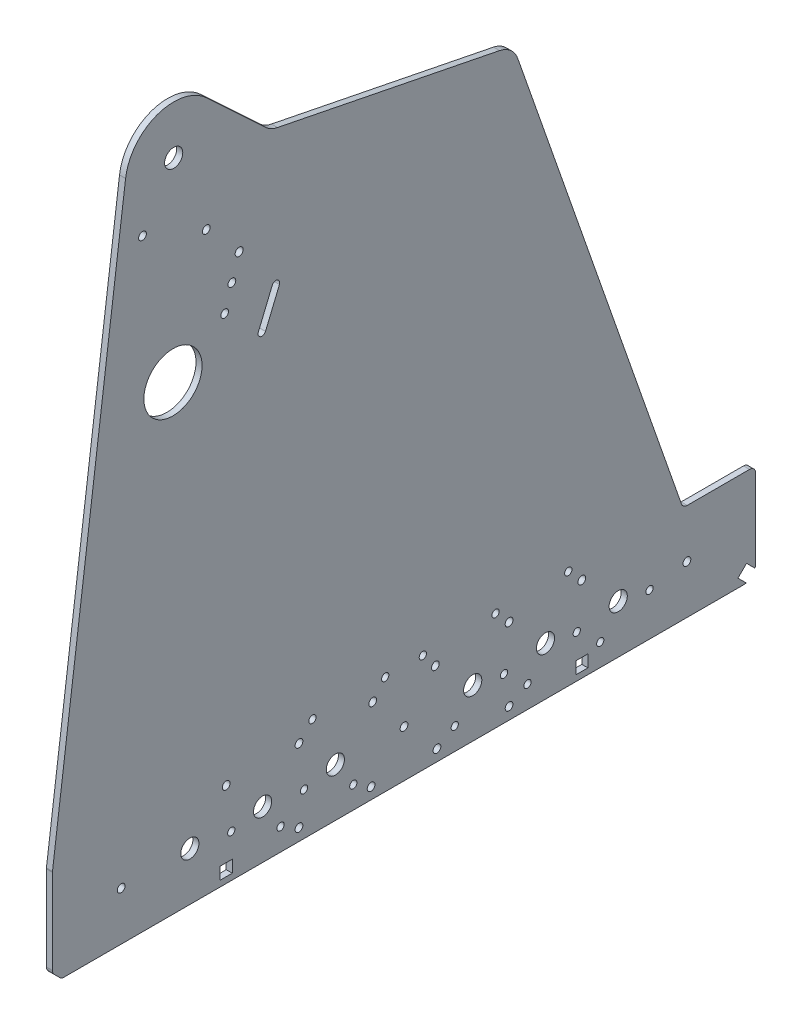
SolidWorks part; units mm, degrees
ref_plane "Front Plane" through (0, 0, 0) normal (0, 0, 1) x (1, 0, 0)
ref_plane "Top Plane" through (0, 0, 0) normal (0, 1, 0) x (1, 0, 0)
ref_plane "Right Plane" through (0, 0, 0) normal (1, 0, 0) x (0, 0, -1)
sketch "Sketch1" plane through (0, 0, 0) normal (1, 0, 0) x (0, 0, -1)
  line L0 (-184.15, -24.6062) -> (184.15, -24.6062)
  line L1 (184.15, -24.6062) -> (184.15, 26.1938)
  line L2 (184.15, 26.1938) -> (146.05, 26.1937)
  line L3 (146.05, 26.1937) -> (57.15, 280.1938)
  line L5 (-145.839, 321.5609) -> (-184.15, 26.1938)
  line L6 (-184.15, 26.1938) -> (-184.15, -24.6062)
  line L7 (-184.15, 350.0437) -> (184.15, 350.0437) construction
  line L8 (57.15, 280.1938) -> (-69.85, 305.5938)
  line L9 (-69.85, 305.5938) -> (-103.3099, 336.854)
  arc A0 (-103.3099, 336.854) -> (-145.839, 321.5609) centre (-120.65, 318.2937) ccw
  point P8 (0, -24.6062)
  dimension "D1" = 368.3
  dimension "D7" = 25.4
  dimension "D2" = 50.8
  dimension "D3" = 38.1
  dimension "D4" = 24.6062
  dimension "D5" = 374.65
  dimension "D6" = 304.8
  dimension "D8" = 342.9
  dimension "D9" = 127
  dimension "D10" = 304.8
  dimension "D11" = 25.4
  dimension "D12" = 127
extrude "Boss-Extrude1" add sketch "Sketch1" along normal blind 3.175
chamfer "Chamfer1" distance 4.7625 angle 45 2 edges at (1.5875, -24.6062, 184.15) (1.5875, -24.6062, -184.15)
fillet "Fillet1" radius 12.7 2 edges at (1.5875, 305.5938, 69.85) (1.5875, 280.1938, -57.15)
fillet "Fillet2" radius 3.175 3 edges at (1.5875, 26.1938, 184.15) (1.5875, 26.1938, -184.15) (1.5875, 26.1937, -146.05)
fillet "Fillet3" radius 3.175 4 edges at (1.5875, -19.8438, -184.15) (1.5875, -24.6062, -179.3875) (1.5875, -19.8437, 184.15) (1.5875, -24.6062, 179.3875)
sketch "Sketch16" plane through (3.175, 0, 0) normal (1, 0, 0) x (0, 0, -1)
  circle A0 centre (112.1746, 0.7937) radius 4.7625
  circle A1 centre (74.0746, 0.7937) radius 4.7625
  circle A2 centre (35.9746, 0.7937) radius 4.7625
  circle A3 centre (-35.9746, 0.7938) radius 4.7625
  circle A4 centre (-74.0746, 0.7938) radius 4.7625
  circle A5 centre (-112.1746, 0.7937) radius 4.7625
  dimension "D1" = 9.525
  dimension "D2" = 9.525
extrude "Cut-Extrude1" cut sketch "Sketch16" against normal up to next
sketch "Sketch25" plane through (3.175, 0, 0) normal (1, 0, 0) x (0, 0, -1)
  circle A0 centre (102.7672, -13.0003) radius 1.905 construction
  circle A1 centre (86.0486, 27.3622) radius 1.905 construction
  circle A2 centre (128.5804, -2.3081) radius 1.905 construction
  circle A3 centre (102.7672, -13.0003) radius 1.905
  circle A4 centre (86.0486, 27.3622) radius 1.905
  circle A5 centre (128.5804, -2.3081) radius 1.905
  circle A6 centre (64.6672, -13.0003) radius 1.905 construction
  circle A8 centre (-9.8486, 27.3622) radius 1.905 construction
  circle A10 centre (-47.9486, 27.3622) radius 1.905 construction
  circle A11 centre (-90.4804, -2.3081) radius 1.905 construction
  circle A12 centre (-64.6672, -13.0003) radius 1.905 construction
  circle A14 centre (-52.3804, -2.3081) radius 1.905 construction
  circle A15 centre (-26.5672, -13.0003) radius 1.905 construction
  circle A16 centre (9.8486, 27.3622) radius 1.905 construction
  circle A17 centre (26.5672, -13.0003) radius 1.905 construction
  circle A18 centre (47.9486, 27.3622) radius 1.905 construction
  circle A19 centre (52.3804, -2.3081) radius 1.905 construction
  circle A20 centre (90.4804, -2.3081) radius 1.905 construction
  circle A21 centre (-9.8486, 27.3622) radius 1.905
  circle A23 centre (-47.9486, 27.3622) radius 1.905
  circle A24 centre (-90.4804, -2.3081) radius 1.905
  circle A25 centre (-64.6672, -13.0003) radius 1.905
  circle A27 centre (-52.3804, -2.3081) radius 1.905
  circle A28 centre (-26.5672, -13.0003) radius 1.905
  circle A29 centre (9.8486, 27.3622) radius 1.905
  circle A30 centre (26.5672, -13.0003) radius 1.905
  circle A31 centre (47.9486, 27.3622) radius 1.905
  circle A32 centre (64.6672, -13.0003) radius 1.905
  circle A33 centre (52.3804, -2.3081) radius 1.905
  circle A34 centre (90.4804, -2.3081) radius 1.905
extrude "Cut-Extrude4" cut sketch "Sketch25" against normal up to next
sketch "Sketch23" plane through (3.175, 0, 0) normal (1, 0, 0) x (0, 0, -1)
  point P0 (-55.0246, -18.3223)
  point P3 (-55.0246, 19.9098)
  point P6 (-93.1246, 19.9098)
  point P9 (-17.2515, -18.6426)
  point P12 (-16.4124, 19.3854)
  point P15 (16.4124, 19.3854)
  point P18 (17.2515, -18.6426)
  point P21 (55.0246, -18.3223)
  point P27 (93.1246, 19.9098)
  point P30 (55.0246, 19.9098)
hole_wizard "#8 (0.16) Diameter Hole1" positions "Sketch23" profile "Sketch24" hole size "#8" standard "ANSI Inch" end condition up to next
sketch "Sketch24" plane through (3.175, -18.3223, 55.0246) normal (0, 1, 0) x (0, 0, -1)
  line L0 (0, 0) -> (0, 3.175)
  line L1 (0, 3.175) -> (2.032, 3.175)
  line L2 (2.032, 3.175) -> (2.032, 0)
  line L5 (2.032, 0) -> (0, 0)
  line L11 (0, -6.35) -> (0, 107.95) construction
  dimension "Thru Hole Dia." = 4.064
  dimension "Thru Hole Depth" = 3.175
sketch "Sketch22" plane through (3.175, 0, 0) normal (1, 0, 0) x (0, 0, -1)
  line L0 (-96.2996, -15.1473) -> (-89.9496, -15.1473) construction
  line L1 (-96.2996, -15.1473) -> (-89.9496, -15.1473)
  line L2 (-96.2996, -15.1473) -> (-96.2996, -21.4973)
  line L3 (-96.2996, -21.4973) -> (-89.9496, -21.4973)
  line L4 (-89.9496, -15.1473) -> (-89.9496, -21.4973)
  line L5 (-96.2996, -15.1473) -> (-89.9496, -21.4973) construction
  line L6 (-96.2996, -21.4973) -> (-89.9496, -15.1473) construction
  line L7 (-89.9496, -15.1473) -> (-89.9496, -19.8734) construction
  line L77 (179.3875, -24.6062) -> (183.8776, -20.1161)
  line L78 (179.3875, -24.6062) -> (174.8974, -20.1161)
  line L79 (183.8776, -20.1161) -> (179.3875, -15.626)
  line L80 (174.8974, -20.1161) -> (179.3875, -15.626)
  line L81 (180.3174, -23.6763) -> (183.2201, -20.7737) construction
  line L82 (-178.0724, -24.6062) -> (178.0724, -24.6062) construction
  line L84 (89.9496, -21.4973) -> (96.2996, -21.4973)
  line L85 (89.9496, -21.4973) -> (89.9496, -15.1473)
  line L86 (89.9496, -15.1473) -> (96.2996, -15.1473)
  line L87 (96.2996, -21.4973) -> (96.2996, -15.1473)
  line L88 (89.9496, -21.4973) -> (96.2996, -15.1473) construction
  line L89 (89.9496, -15.1473) -> (96.2996, -21.4973) construction
  point P0 (-93.1246, -18.3223)
  point P19 (93.1246, -18.3223)
  dimension "D1" = 6.35
  dimension "D2" = 6.35
extrude "Cut-Extrude3" cut sketch "Sketch22" against normal up to next
sketch "Sketch21" plane through (3.175, 0, 0) normal (1, 0, 0) x (0, 0, -1)
  circle A0 centre (-148.1579, 0.7937) radius 2.032
  circle A2 centre (0, 0) radius 2.032
  circle A3 centre (148.1579, 0.7938) radius 2.032
  dimension "D1" = 4.064
extrude "Cut-Extrude2" cut sketch "Sketch21" against normal up to next
sketch "Sketch26" plane through (3.175, 0, 0) normal (1, 0, 0) x (0, 0, -1)
  line L0 (-145.839, 321.5609) -> (-184.1236, 26.3971) construction
  line L1 (-178.0724, -24.6062) -> (178.0724, -24.6062) construction
  circle A0 centre (-121.0218, 216.6937) radius 15.24
  dimension "D1" = 30.48
  dimension "D2" = 38.1
  dimension "D3" = 241.3
extrude "Cut-Extrude5" cut sketch "Sketch26" against normal through all
sketch "Sketch27" plane through (3.175, 0, 0) normal (1, 0, 0) x (0, 0, -1)
  circle A0 centre (-120.65, 318.2937) radius 4.7625
  dimension "D1" = 9.525
extrude "Cut-Extrude6" cut sketch "Sketch27" against normal through all
sketch "Sketch28" plane through (3.175, 0, 0) normal (1, 0, 0) x (0, 0, -1)
  line L0 (-120.65, 318.2937) -> (-103.5612, 277.2599) construction
  line L1 (-103.5612, 277.2599) -> (-86.3654, 258.566) construction
  line L2 (-86.3654, 258.566) -> (-90.1612, 246.4465) construction
  line L3 (-90.1612, 246.4465) -> (-93.9569, 234.327) construction
  line L4 (-145.839, 321.5609) -> (-184.1236, 26.3971) construction
  circle A0 centre (-93.9569, 234.327) radius 2.032
  circle A1 centre (-90.1612, 246.4465) radius 2.032
  circle A2 centre (-86.3654, 258.566) radius 2.0955
  circle A3 centre (-103.5612, 277.2599) radius 2.032
  dimension "D4" = 4.064
  dimension "D5" = 4.191
  dimension "D6" = 4.064
  dimension "D1" = 25.4
  dimension "D2" = 44.45
  dimension "D3" = 12.7
  dimension "D7" = 30
  dimension "D8" = 120
  dimension "D9" = 160
extrude "Cut-Extrude7" cut sketch "Sketch28" against normal through all
sketch "Sketch29" plane through (3.175, 0, 0) normal (1, 0, 0) x (0, 0, -1)
  line L0 (-145.839, 321.5609) -> (-184.1236, 26.3971) construction
  line L1 (-67.1375, 233.9197) -> (-74.4276, 216.3198) construction
  line L2 (-65.2602, 233.1421) -> (-72.5503, 215.5422)
  line L3 (-69.0148, 234.6973) -> (-76.305, 217.0974)
  line L4 (-67.1375, 233.9197) -> (-67.1375, 253.7354) construction
  circle A0 centre (-136.9875, 291.0697) radius 2.032
  circle A2 centre (-120.65, 318.2937) radius 4.7625 construction
  arc A4 (-65.2602, 233.1421) -> (-69.0148, 234.6973) centre (-67.1375, 233.9197) ccw
  arc A5 (-76.305, 217.0974) -> (-72.5503, 215.5422) centre (-74.4276, 216.3198) ccw
  point P8 (-70.7826, 225.1198)
  dimension "D1" = 31.75
  dimension "D2" = 4.064
  dimension "D3" = 69.85
  dimension "D4" = 12.7
  dimension "D5" = 57.15
  dimension "D6" = 19.05
  dimension "D7" = 22.5
extrude "Cut-Extrude8" cut sketch "Sketch29" against normal through all
